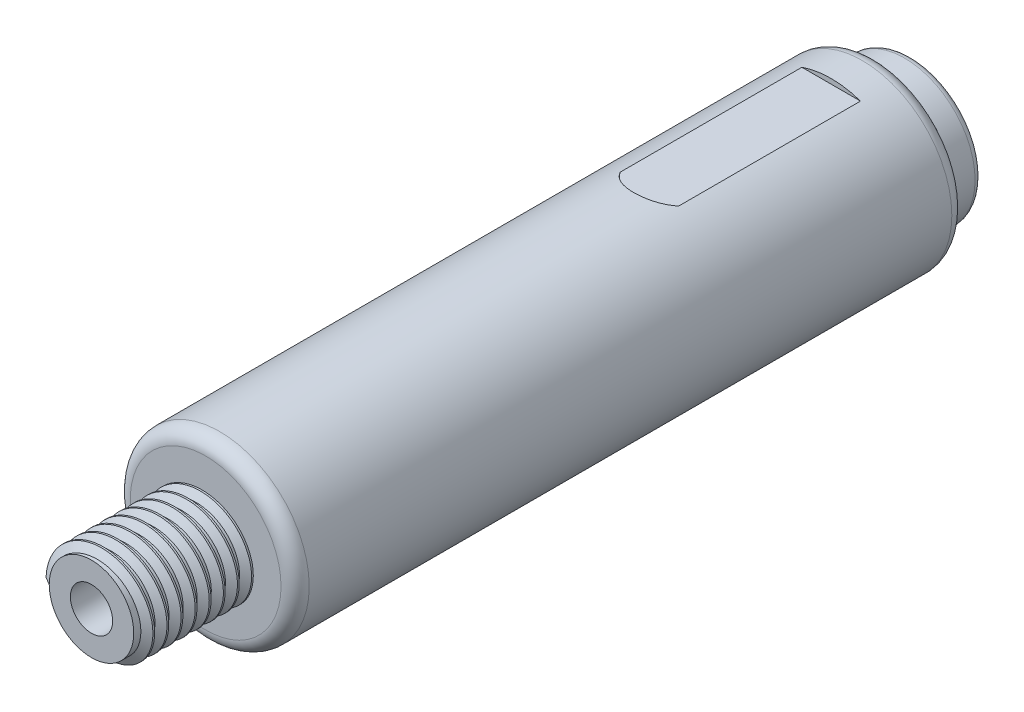
SolidWorks part; units mm, degrees
material "AISI 304"
ref_plane "Front Plane" through (0, 0, 0) normal (0, 0, 1) x (1, 0, 0)
ref_plane "Top Plane" through (0, 0, 0) normal (0, 1, 0) x (1, 0, 0)
ref_plane "Right Plane" through (0, 0, 0) normal (1, 0, 0) x (0, 0, -1)
other "Configuration Table"
sketch "Sketch2" plane through (0, 0, 0) normal (1, 0, 0) x (0, 0, -1)
  line L0 (0, 0) -> (26.2978, 0) construction
  line L1 (23.8, 3) -> (26.3, 3)
  line L2 (23.8, 3) -> (23.8, 5)
  line L3 (23.8, 5) -> (26.3, 5)
  line L4 (26.3, 3) -> (26.3, 5)
  line L5 (23.8, 3) -> (-23.8, 3)
  line L6 (23.8, 3) -> (23.8, 6.35)
  line L7 (23.8, 6.35) -> (-23.8, 6.35)
  line L8 (-23.8, 3) -> (-23.8, 6.35)
  line L9 (-23.8, 3) -> (-31.9, 3)
  line L10 (-23.8, 3) -> (-23.8, 1.5)
  line L11 (-23.8, 1.5) -> (-31.9, 1.5)
  line L12 (-31.9, 3) -> (-31.9, 1.5)
  line L13 (0, 0) -> (0, 6.35) construction
  line L14 (25.05, 5) -> (25.05, 0) construction
  line L15 (-31.9, 1.5) -> (-31.9, 0) construction
  line L16 (-23.8, 1.5) -> (-15.8, 3)
  point P17 (25.05, 3)
  point P19 (0, 6.35)
  dimension "D1" = 2.5
  dimension "D2" = 47.6
  dimension "D3" = 55.7
  dimension "D4" = 6.35
  dimension "D5" = 3
  dimension "D6" = 1.5
  dimension "D7" = 8
  dimension "D8" = 5
revolve "Revolve1" add sketch "Sketch2" angle 360 about L0 region at (0, 4, -25.05) region at (0, 4.675, 0) region at (0, 2.5, 21.1333) region at (0, 2.25, 27.85)
fillet "Fillet1" radius 1 2 edges at (6.35, 0, 23.8) (6.35, 0, -23.8)
fillet "Fillet2" radius 0.5 1 edges at (5, 0, -26.3)
thread "Thread1" pitch 1 method extrude profile "Thread Profile1" start angle 0, offset 0, length 8, pitch 1, diameter 6
ref_plane "Plane1" through (-3, 0, 31.9) normal (0, -1, 0) x (-1, 0, 0)
sketch "Thread Profile1" plane through (-3, 0, 31.9) normal (0, -1, 0) x (-1, 0, 0)
  line L0 (0, 0) -> (0, 1) construction
  line L1 (0, 0) -> (0.5413, 0.3125)
  line L2 (0.5413, 0.3125) -> (0.5413, 0.4375)
  line L3 (0.5413, 0.4375) -> (0, 0.75)
  line L4 (0.5413, 0.375) -> (0, 0.375) construction
  line L11 (0, 0) -> (0, 0.75)
  point P2 (0, 0)
  dimension "Pitch" = 1
  dimension "Profile_Angle" = 60
  dimension "Profile_Land" = 0.125
  dimension "Profile_Height" = 0.5413
ref_plane "Plane2" through (0, 6, 0) normal (0, 1, 0) x (1, 0, 0)
sketch "Sketch6" plane through (0, 6, 0) normal (0, 1, 0) x (1, 0, 0)
  line L1 (-2.484, 9.055) -> (2.484, 9.055)
  line L2 (-2.484, 9.055) -> (-2.484, 20.5883)
  line L3 (-2.484, 20.5883) -> (2.484, 20.5883)
  line L4 (2.484, 9.055) -> (2.484, 20.5883)
  line L5 (-2.484, 9.055) -> (2.484, 20.5883) construction
  line L6 (-2.484, 20.5883) -> (2.484, 9.055) construction
  arc A0 (-2.484, 9.055) -> (2.484, 9.055) centre (0, 9.055) ccw
  point P0 (0, 14.8216)
  point P5 (0, 0)
extrude "Cut-Extrude1" cut sketch "Sketch6" along normal blind 10 contours L1 A0 | L1 L4 L3 L2 region at (0, 6, -14.8216) region at (0, 6, -8.0008)
